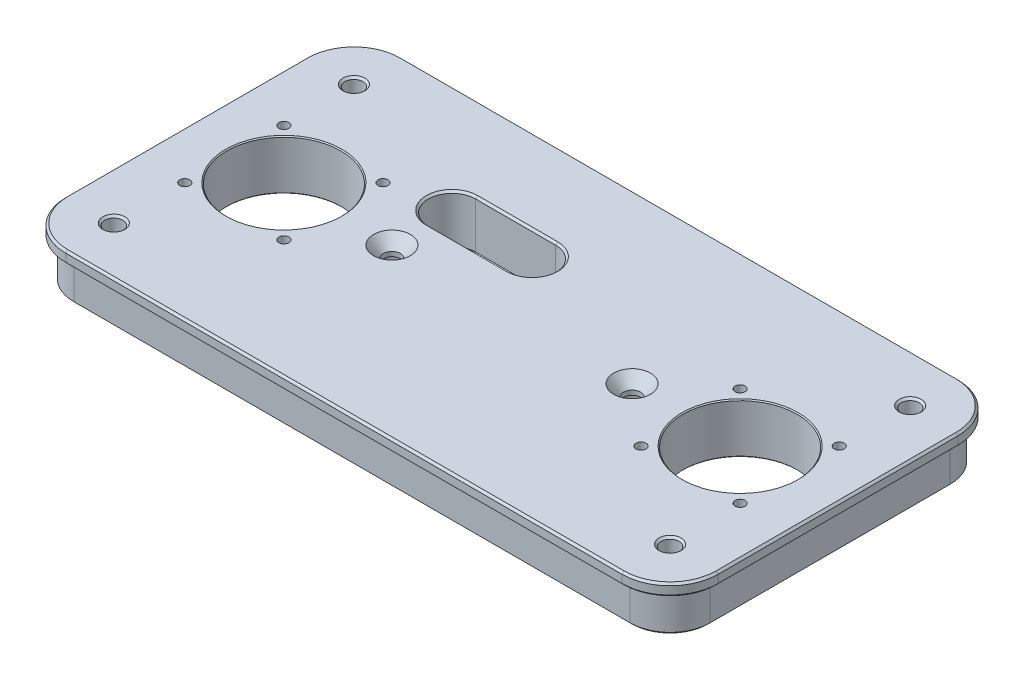
SolidWorks part; units mm, degrees
material "6061-T6 Aluminum"
ref_plane "Front Plane" through (0, 0, 0) normal (0, 0, 1) x (1, 0, 0)
ref_plane "Top Plane" through (0, 0, 0) normal (0, 1, 0) x (1, 0, 0)
ref_plane "Right Plane" through (0, 0, 0) normal (1, 0, 0) x (0, 0, -1)
sketch "Sketch1" plane through (0, 0, 0) normal (0, 1, 0) x (1, 0, 0)
  line L1 (-159, -80) -> (159, -80)
  line L2 (-159, -80) -> (-159, 80)
  line L3 (-159, 80) -> (159, 80)
  line L4 (159, -80) -> (159, 80)
  line L5 (-159, -80) -> (159, 80) construction
  line L6 (-159, 80) -> (159, -80) construction
  point P0 (0, 0)
  dimension "D1" = 160
  dimension "D2" = 318
extrude "Boss-Extrude1" add sketch "Sketch1" along normal blind 25
sketch "Sketch2" plane through (0, 25, 0) normal (0, 1, 0) x (1, 0, 0)
  line L0 (-114, 0) -> (0, 0) construction
  line L1 (0, 0) -> (114, 0) construction
  circle A0 centre (-114, 0) radius 28.5
  circle A1 centre (114, 0) radius 28.5
  dimension "D1" = 228
  dimension "D2" = 57
extrude "Cut-Extrude1" cut sketch "Sketch2" against normal through all
sketch "Sketch4" plane through (0, 25, 0) normal (0, 1, 0) x (1, 0, 0)
  line L0 (60, 0) -> (0, 0) construction
  line L1 (0, 0) -> (-60, 0) construction
  circle A0 centre (-60, 0) radius 9.55
  circle A1 centre (60, 0) radius 9.55
  dimension "D1" = 19.1
  dimension "D2" = 120
extrude "Cut-Extrude2" cut sketch "Sketch4" against normal through all both and the other way through all
chamfer "Chamfer1" distance 0.5 angle 45 8 edges at (114, 25, 28.5) (114, 0, 28.5) (60, 25, -9.55) (60, 0, 9.55) (-60, 25, -9.55) (-60, 0, 9.55) (-114, 25, 28.5) (-114, 0, 28.5)
fillet "Fillet1" radius 20 4 edges at (159, 12.5, 80) (159, 12.5, -80) (-159, 12.5, -80) (-159, 12.5, 80)
hole_wizard "M8 Clearance Hole1" positions "Sketch5" profile "Sketch6" hole size "M8" standard "ANSI Metric" end condition through all
sketch "Sketch5" plane through (0, 0, 0) normal (0, 1, 0) x (1, 0, 0)
  point P0 (-139, 60)
  point P3 (-139, -60)
  point P6 (139, 60)
  point P9 (139, -60)
sketch "Sketch6" plane through (-139, 0, -60) normal (1, 0, 0) x (0, 0, -1)
  line L0 (0, 0) -> (0, 25)
  line L1 (0, 25) -> (4.5, 25)
  line L2 (4.5, 25) -> (4.5, 0)
  line L5 (4.5, 0) -> (0, 0)
  line L11 (0, -6.35) -> (0, 107.95) construction
  dimension "Thru Hole Dia." = 9
  dimension "Thru Hole Depth" = 25
sketch "Sketch7" plane through (0, 0, 0) normal (0, -1, 0) x (1, 0, 0)
  line L1 (89.235, 24.765) -> (138.765, 24.765) construction
  line L2 (89.235, 24.765) -> (89.235, -24.765) construction
  line L3 (89.235, -24.765) -> (138.765, -24.765) construction
  line L4 (138.765, 24.765) -> (138.765, -24.765) construction
  line L5 (89.235, 24.765) -> (138.765, -24.765) construction
  line L6 (89.235, -24.765) -> (138.765, 24.765) construction
  line L7 (-138.765, 24.765) -> (-89.235, 24.765) construction
  line L8 (-138.765, 24.765) -> (-138.765, -24.765) construction
  line L9 (-138.765, -24.765) -> (-89.235, -24.765) construction
  line L10 (-89.235, 24.765) -> (-89.235, -24.765) construction
  line L11 (-138.765, 24.765) -> (-89.235, -24.765) construction
  line L12 (-138.765, -24.765) -> (-89.235, 24.765) construction
  circle A0 centre (89.235, 24.765) radius 3.302 construction
  circle A1 centre (138.765, -24.765) radius 3.302 construction
  circle A2 centre (138.765, 24.765) radius 3.302 construction
  circle A3 centre (89.235, -24.765) radius 3.302 construction
  circle A4 centre (89.235, 24.765) radius 3.302
  circle A5 centre (138.765, -24.765) radius 3.302
  circle A6 centre (138.765, 24.765) radius 3.302
  circle A7 centre (89.235, -24.765) radius 3.302
  circle A12 centre (-138.765, -24.765) radius 3.302
  circle A13 centre (-89.235, -24.765) radius 3.302
  circle A14 centre (-89.235, 24.765) radius 3.302
  circle A15 centre (-138.765, 24.765) radius 3.302
  point P13 (114, 0)
  point P15 (-114, 0)
hole_wizard "M6x1.0 Tapped Hole1" positions "Sketch8" profile "Sketch9" tap size "M6x1.0" standard "ANSI Metric" end condition through all
sketch "Sketch8" plane through (0, 0, 0) normal (0, -1, 0) x (-1, 0, 0)
  point P0 (138.765, -24.765)
  point P3 (89.235, -24.765)
  point P6 (89.235, 24.765)
  point P9 (138.765, 24.765)
  point P12 (-89.235, -24.765)
  point P15 (-138.765, -24.765)
  point P18 (-89.235, 24.765)
  point P21 (-138.765, 24.765)
cosmetic thread "Hole Thread11" parameters "D2"=6
cosmetic thread "Hole Thread12" parameters "D2"=6
cosmetic thread "Hole Thread13" parameters "D2"=6
cosmetic thread "Hole Thread14" parameters "D2"=6
cosmetic thread "Hole Thread16" parameters "D2"=6
sketch "Sketch9" plane through (-138.765, 0, 24.765) normal (1, 0, 0) x (0, 0, -1)
  line L0 (0, 0) -> (0, 25)
  line L1 (0, 25) -> (2.5, 25)
  line L2 (2.5, 25) -> (2.5, 0)
  line L5 (2.5, 0) -> (0, 0)
  line L11 (0, -6.35) -> (0, 107.95) construction
  dimension "Thru Tap Drill Dia." = 5
  dimension "Thru Tap Drill Depth" = 25
cosmetic thread "Hole Thread17" parameters "D2"=6
cosmetic thread "Hole Thread18" parameters "D2"=6
cosmetic thread "Hole Thread19" parameters "D2"=6
sketch "Sketch13" plane through (0, 25, 0) normal (0, 1, 0) x (1, 0, 0)
  circle A0 centre (60, 0) radius 13.411
  circle A1 centre (-60, 0) radius 14.7245
extrude "Boss-Extrude3" add sketch "Sketch13" against normal blind 8
hole_wizard "CSK for 5/16 Flat Head Socket Cap Screw1" positions "Sketch14" profile "Sketch15" countersink size "5/16" standard "ANSI Inch" end condition through all
sketch "Sketch14" plane through (0, 25, 0) normal (0, 1, 0) x (1, 0, 0)
  point P0 (60, 0)
  point P3 (-60, 0)
sketch "Sketch15" plane through (60, 25, 0) normal (1, 0, 0) x (0, 0, 1)
  line L0 (0, 0) -> (0, 25)
  line L1 (0, 25) -> (4.2164, 25)
  line L2 (4.2164, 25) -> (4.2164, 5.7335)
  line L3 (4.2164, 5.7335) -> (9.2005, 0)
  line L5 (9.2005, 0) -> (0, 0)
  line L6 (-4.2164, 5.7335) -> (-9.2005, 0) construction
  line L11 (0, -6.35) -> (0, 107.95) construction
  dimension "Thru Hole Dia." = 8.4328
  dimension "Thru Hole Depth" = 25
  dimension "Near C'Sink Dia." = 18.401
  dimension "Near C'Sink Angle" = 82
sketch "Sketch16" plane through (0, 25, 0) normal (0, -1, 0) x (1, 0, 0)
  line L4 (159, 60) -> (159, -60) construction
  line L5 (139, -80) -> (-139, -80) construction
  line L6 (-159, -60) -> (-159, 60) construction
  line L7 (-139, 80) -> (139, 80) construction
  line L8 (163, -60) -> (163, 60)
  line L9 (139, 84) -> (-139, 84)
  line L10 (-163, 60) -> (-163, -60)
  line L11 (-139, -84) -> (139, -84)
  line L12 (163, -60) -> (163, 60)
  line L13 (139, 84) -> (-139, 84)
  line L14 (-163, 60) -> (-163, -60)
  line L15 (-139, -84) -> (139, -84)
  line L16 (159, 60) -> (159, -60)
  line L17 (139, -80) -> (-139, -80)
  line L18 (-159, -60) -> (-159, 60)
  line L19 (-139, 80) -> (139, 80)
  arc A4 (159, 60) -> (139, 80) centre (139, 60) ccw construction
  arc A5 (139, -80) -> (159, -60) centre (139, -60) ccw construction
  arc A6 (-159, -60) -> (-139, -80) centre (-139, -60) ccw construction
  arc A7 (-139, 80) -> (-159, 60) centre (-139, 60) ccw construction
  arc A8 (163, 60) -> (139, 84) centre (139, 60) ccw
  arc A9 (-139, 84) -> (-163, 60) centre (-139, 60) ccw
  arc A10 (-163, -60) -> (-139, -84) centre (-139, -60) ccw
  arc A11 (139, -84) -> (163, -60) centre (139, -60) ccw
  arc A12 (163, 60) -> (139, 84) centre (139, 60) ccw
  arc A13 (-139, 84) -> (-163, 60) centre (-139, 60) ccw
  arc A14 (-163, -60) -> (-139, -84) centre (-139, -60) ccw
  arc A15 (139, -84) -> (163, -60) centre (139, -60) ccw
  arc A16 (159, 60) -> (139, 80) centre (139, 60) ccw
  arc A17 (139, -80) -> (159, -60) centre (139, -60) ccw
  arc A18 (-159, -60) -> (-139, -80) centre (-139, -60) ccw
  arc A19 (-139, 80) -> (-159, 60) centre (-139, 60) ccw
  dimension "D1" = 4
extrude "Boss-Extrude4" add sketch "Sketch16" along normal blind 6
sketch "Sketch17" plane through (0, 0, 0) normal (0, -1, 0) x (1, 0, 0)
  line L0 (-60, -30.0192) -> (-20, -30.0192) construction
  line L1 (-60, -18.1841) -> (-20, -18.1841)
  line L2 (-60, -41.8544) -> (-20, -41.8544)
  circle A0 centre (-60, -30.0192) radius 9.2363 construction
  arc A1 (-69.9426, -35.7596) -> (-50.0574, -35.7596) centre (-60, -30.0192) ccw construction
  arc A2 (-60, -18.1841) -> (-60, -41.8544) centre (-60, -30.0192) ccw
  arc A3 (-20, -41.8544) -> (-20, -18.1841) centre (-20, -30.0192) ccw
  point P2 (-40, -30.0192)
  dimension "D1" = 40
extrude "Cut-Extrude3" cut sketch "Sketch17" against normal through all
chamfer "Chamfer4" distance 1 angle 45 40 edges at (139, 0, -64.5) (139, 25, -64.5) (-139, 0, -64.5) (-139, 25, -64.5) (139, 0, 55.5) (139, 25, 55.5) (-139, 0, 55.5) (-139, 25, 55.5) (0, 19, -84) (155.9706, 19, -76.9706) (-155.9706, 19, -76.9706) (163, 19, 0) (-163, 19, 0) (155.9706, 19, 76.9706) (-155.9706, 19, 76.9706) (0, 19, 84) (0, 25, -84) (155.9706, 25, -76.9706) (-155.9706, 25, -76.9706) (163, 25, 0) (-163, 25, 0) (155.9706, 25, 76.9706) (-155.9706, 25, 76.9706) (0, 25, 84) (-40, 25, -18.1841) (-71.8351, 25, -30.0192) (-8.1649, 25, -30.0192) (-40, 25, -41.8544) (-40, 0, -18.1841) (-71.8351, 0, -30.0192) (-8.1649, 0, -30.0192) (-40, 0, -41.8544) (0, 0, -80) (-153.1421, 0, -74.1421) (153.1421, 0, -74.1421) (-159, 0, 0) (159, 0, 0) (-153.1421, 0, 74.1421) (153.1421, 0, 74.1421) (0, 0, 80)
